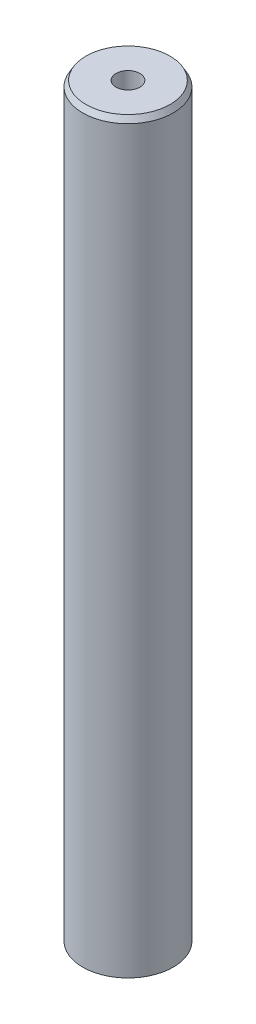
SolidWorks part; units mm, degrees
ref_plane "Front Plane" through (0, 0, 0) normal (0, 0, 1) x (1, 0, 0)
ref_plane "Top Plane" through (0, 0, 0) normal (0, 1, 0) x (1, 0, 0)
ref_plane "Right Plane" through (0, 0, 0) normal (1, 0, 0) x (0, 0, -1)
sketch "Sketch1" plane through (0, 0, 0) normal (0, 1, 0) x (1, 0, 0)
  circle A0 centre (0, 0) radius 7.5
  dimension "SHAFT_OD" = 15
extrude "Boss-Extrude1" add sketch "Sketch1" along normal blind 124.0668
sketch "Sketch2" plane through (0, 0, 0) normal (0, 1, 0) x (1, 0, 0)
  circle A0 centre (0, 0) radius 1.9786
  dimension "BORE_D" = 3.9572
extrude "Cut-Extrude1" cut sketch "Sketch2" along normal through all
chamfer "Chamfer1" distance 0.9353 angle 30 2 edges at (0, 124.0668, 7.5) (0, 0, 7.5) first distance on face at (0, 124.0668, 7.5) first distance on face at (0, 0, 1.9786)
